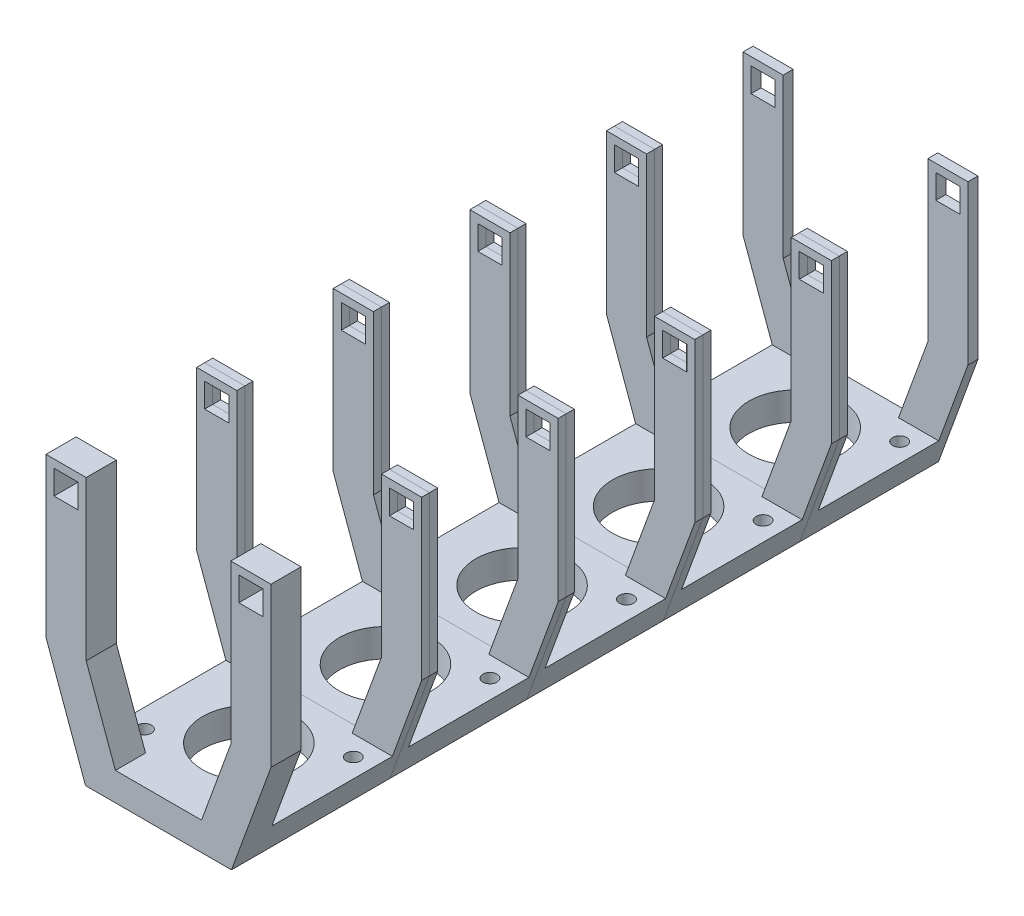
SolidWorks part; units mm, degrees
ref_plane "Front Plane" through (0, 0, 0) normal (0, 0, 1) x (1, 0, 0)
ref_plane "Top Plane" through (0, 0, 0) normal (0, 1, 0) x (1, 0, 0)
ref_plane "Right Plane" through (0, 0, 0) normal (1, 0, 0) x (0, 0, -1)
sketch "Sketch3" plane through (0, 0, 0) normal (0, 0, 1) x (1, 0, 0)
  line L0 (0, 0) -> (46, 0) construction
  line L1 (-3, -3) -> (3, -3) construction
  line L2 (-3, -3) -> (-3, 3) construction
  line L3 (-3, 3) -> (3, 3) construction
  line L4 (3, -3) -> (3, 3) construction
  line L5 (-3, -3) -> (3, 3) construction
  line L6 (-3, 3) -> (3, -3) construction
  line L7 (43, -3) -> (49, -3) construction
  line L8 (43, -3) -> (43, 3) construction
  line L9 (43, 3) -> (49, 3) construction
  line L10 (49, -3) -> (49, 3) construction
  line L11 (43, -3) -> (49, 3) construction
  line L12 (43, 3) -> (49, -3) construction
  line L14 (5, -5) -> (5, 5)
  line L16 (-5, -5) -> (-5, 5)
  line L18 (51, -5) -> (51, 5)
  line L20 (41, -5) -> (41, 5)
  line L21 (-5, -5) -> (-5, -25) construction
  line L22 (-5, -25) -> (51, -25) construction
  line L23 (51, -25) -> (51, -5) construction
  line L24 (23, 0) -> (23, 5) construction
  line L25 (23, 5) -> (8, 5) construction
  line L26 (23, 5) -> (38, 5) construction
  line L27 (8, 5) -> (8, -25) construction
  line L28 (38, 5) -> (38, -25) construction
  line L29 (-5, -5) -> (4.8272, -32)
  line L30 (4.8272, -32) -> (41.1728, -32)
  line L31 (41.1728, -32) -> (51, -5)
  line L32 (5, -5) -> (12.2794, -25)
  line L33 (12.2794, -25) -> (33.7206, -25)
  line L34 (33.7206, -25) -> (41, -5)
  line L35 (2.2794, -25) -> (12.2794, -25)
  line L36 (-5, -5) -> (5, -5) construction
  line L37 (41, -5) -> (51, -5) construction
  line L38 (33.7206, -25) -> (43.7206, -25)
  line L39 (-5, 5) -> (5, 5) construction
  line L40 (41, 5) -> (51, 5) construction
  line L41 (-5, 5) -> (-5, 34.5)
  line L42 (-5, 34.5) -> (5, 34.5)
  line L43 (5, 34.5) -> (5, 5)
  line L44 (41, 5) -> (41, 34.5)
  line L45 (41, 34.5) -> (51, 34.5)
  line L46 (51, 34.5) -> (51, 5)
  line L48 (-3, 26.5) -> (3, 26.5)
  line L49 (-3, 26.5) -> (-3, 32.5)
  line L50 (-3, 32.5) -> (3, 32.5)
  line L51 (3, 26.5) -> (3, 32.5)
  line L52 (-3, 26.5) -> (3, 32.5) construction
  line L53 (-3, 32.5) -> (3, 26.5) construction
  line L54 (43, 26.5) -> (49, 26.5)
  line L55 (43, 26.5) -> (43, 32.5)
  line L56 (43, 32.5) -> (49, 32.5)
  line L57 (49, 26.5) -> (49, 32.5)
  line L58 (43, 26.5) -> (49, 32.5) construction
  line L59 (43, 32.5) -> (49, 26.5) construction
  point P0 (0, 0)
  point P6 (46, 0)
  point P27 (2.2794, -25)
  point P34 (43.7206, -25)
  point P35 (0, 29.5)
  point P46 (46, 29.5)
  point P51 (0, 0)
  point P52 (0, 0)
  dimension "D1" = 40
  dimension "D2" = 6
  dimension "D4" = 30
  dimension "D5" = 30
  dimension "D6" = 7
  dimension "D7" = 20
  dimension "D8" = 20
  dimension "D9" = 20
  dimension "D10" = 20
  dimension "D11" = 29.5
  dimension "D12" = 29.5
  dimension "D13" = 2
  dimension "D14" = 2
  dimension "D3" = 2
extrude "Boss-Extrude1" add sketch "Sketch3" along normal blind 2 contours L29 L35 L32 L14 L16 L4 L1 L2 L3 | L34 L38 L31 L18 L20 L10 L7 L8 L9 | L38 L33 L35 L29 L30 L31 region at (1.3022, 3.1561, 0) region at (23, -28.4236, 0) region at (44.6978, 3.1561, 0)
extrude "Boss-Extrude2" add sketch "Sketch3<4>" against normal blind 30 contours L38 L33 L35 L29 L30 L31 region at (23, -28.4236, 0)
sketch "Sketch3<4>" plane through (0, 0, 0) normal (0, 0, 1) x (1, 0, 0) same geometry as "Sketch3"
sketch "Sketch4" plane through (0, 0, -30) normal (0, 0, -1) x (-1, 0, 0)
  line L0 (5, -5) -> (5, 34.5) construction
  line L2 (-5, -5) -> (-5, 34.5) construction
  line L3 (-5, -5) -> (-12.2794, -25) construction
  line L4 (5, -5) -> (-2.2794, -25) construction
  line L5 (-2.2794, -25) -> (-4.8272, -32) construction
  line L6 (-41.1728, -32) -> (-43.7206, -25) construction
  line L7 (-4.8272, -32) -> (-41.1728, -32) construction
  line L8 (-2.2794, -25) -> (-43.7206, -25) construction
  line L9 (-33.7206, -25) -> (-41, -5) construction
  line L10 (-41, -5) -> (-41, 34.5) construction
  line L11 (-43.7206, -25) -> (-51, -5) construction
  line L12 (-51, -5) -> (-51, 34.5) construction
  line L13 (3, 26.5) -> (-3, 26.5) construction
  line L14 (5, -5) -> (5, 34.5)
  line L16 (-5, -5) -> (-5, 34.5)
  line L17 (-5, -5) -> (-12.2794, -25)
  line L18 (5, -5) -> (-2.2794, -25)
  line L19 (-2.2794, -25) -> (-4.8272, -32)
  line L20 (-41.1728, -32) -> (-43.7206, -25)
  line L21 (-4.8272, -32) -> (-41.1728, -32)
  line L22 (-12.2794, -25) -> (-33.7206, -25)
  line L23 (-33.7206, -25) -> (-41, -5)
  line L24 (-41, -5) -> (-41, 34.5)
  line L25 (-43.7206, -25) -> (-51, -5)
  line L26 (-51, -5) -> (-51, 34.5)
  line L44 (-51, 34.5) -> (-41, 34.5)
  line L45 (-5, 34.5) -> (5, 34.5)
  line L46 (3, 26.5) -> (3, 32.5) construction
  line L47 (3, 32.5) -> (-3, 32.5) construction
  line L48 (-3, 26.5) -> (-3, 32.5) construction
  line L49 (-49, 26.5) -> (-49, 32.5) construction
  line L50 (-43, 26.5) -> (-49, 26.5) construction
  line L51 (-43, 26.5) -> (-43, 32.5) construction
  line L52 (-43, 32.5) -> (-49, 32.5) construction
  line L53 (3, 26.5) -> (-3, 26.5)
  line L54 (3, 26.5) -> (3, 32.5)
  line L55 (3, 32.5) -> (-3, 32.5)
  line L56 (-3, 26.5) -> (-3, 32.5)
  line L57 (-49, 26.5) -> (-49, 32.5)
  line L58 (-43, 26.5) -> (-49, 26.5)
  line L59 (-43, 26.5) -> (-43, 32.5)
  line L60 (-43, 32.5) -> (-49, 32.5)
extrude "Boss-Extrude6" add sketch "Sketch4" along normal blind 2
pattern_linear "LPattern7" count 5 spacing 34 along (0, 0, 1) of bodies 128
sketch "Sketch12" plane through (0, 0, -32) normal (0, 0, -1) x (-1, 0, 0)
  line L0 (-5, 34.5) -> (-5, -5) construction
  line L1 (5, 34.5) -> (-5, 34.5) construction
  line L2 (5, -5) -> (5, 34.5) construction
  line L7 (-5, -5) -> (-12.2794, -25) construction
  line L8 (-4.8272, -32) -> (5, -5) construction
  line L9 (-12.2794, -25) -> (-33.7206, -25) construction
  line L10 (-41.1728, -32) -> (-4.8272, -32) construction
  line L11 (-41, -5) -> (-41, 34.5) construction
  line L12 (-33.7206, -25) -> (-41, -5) construction
  line L13 (-51, -5) -> (-41.1728, -32) construction
  line L18 (-51, 34.5) -> (-51, -5) construction
  line L19 (-41, 34.5) -> (-51, 34.5) construction
  line L20 (-5, 34.5) -> (-5, -5)
  line L21 (5, 34.5) -> (-5, 34.5)
  line L22 (5, -5) -> (5, 34.5)
  line L27 (-5, -5) -> (-12.2794, -25)
  line L28 (-4.8272, -32) -> (5, -5)
  line L29 (-12.2794, -25) -> (-33.7206, -25)
  line L30 (-41.1728, -32) -> (-4.8272, -32)
  line L31 (-41, -5) -> (-41, 34.5)
  line L32 (-33.7206, -25) -> (-41, -5)
  line L33 (-51, -5) -> (-41.1728, -32)
  line L38 (-51, 34.5) -> (-51, -5)
  line L39 (-41, 34.5) -> (-51, 34.5)
  line L40 (-3, 26.5) -> (3, 26.5) construction
  line L41 (3, 26.5) -> (3, 32.5) construction
  line L42 (3, 32.5) -> (-3, 32.5) construction
  line L43 (-3, 32.5) -> (-3, 26.5) construction
  line L44 (-49, 32.5) -> (-49, 26.5) construction
  line L45 (-49, 26.5) -> (-43, 26.5) construction
  line L46 (-43, 26.5) -> (-43, 32.5) construction
  line L47 (-43, 32.5) -> (-49, 32.5) construction
  line L48 (-3, 26.5) -> (3, 26.5)
  line L49 (3, 26.5) -> (3, 32.5)
  line L50 (3, 32.5) -> (-3, 32.5)
  line L51 (-3, 32.5) -> (-3, 26.5)
  line L52 (-49, 32.5) -> (-49, 26.5)
  line L53 (-49, 26.5) -> (-43, 26.5)
  line L54 (-43, 26.5) -> (-43, 32.5)
  line L55 (-43, 32.5) -> (-49, 32.5)
extrude "Boss-Extrude7" add sketch "Sketch12" along normal blind 0.5
sketch "Sketch13" plane through (0, 0, 138) normal (0, 0, 1) x (1, 0, 0)
  line L1 (41, -5) -> (41, 34.5) construction
  line L4 (51, -5) -> (51, 34.5) construction
  line L7 (41.1728, -32) -> (51, -5) construction
  line L8 (33.7206, -25) -> (41, -5) construction
  line L9 (4.8272, -32) -> (41.1728, -32) construction
  line L10 (12.2794, -25) -> (33.7206, -25) construction
  line L11 (5, -5) -> (12.2794, -25) construction
  line L12 (-5, -5) -> (4.8272, -32) construction
  line L13 (5, -5) -> (5, 34.5) construction
  line L18 (-5, -5) -> (-5, 34.5) construction
  line L21 (41, -5) -> (41, 34.5)
  line L24 (51, -5) -> (51, 34.5)
  line L27 (41.1728, -32) -> (51, -5)
  line L28 (33.7206, -25) -> (41, -5)
  line L29 (4.8272, -32) -> (41.1728, -32)
  line L30 (12.2794, -25) -> (33.7206, -25)
  line L31 (5, -5) -> (12.2794, -25)
  line L32 (-5, -5) -> (4.8272, -32)
  line L33 (5, -5) -> (5, 34.5)
  line L38 (-5, -5) -> (-5, 34.5)
  line L40 (-5, 34.5) -> (5, 34.5)
  line L41 (41, 34.5) -> (51, 34.5)
  line L42 (43, 26.5) -> (43, 32.5) construction
  line L43 (43, 26.5) -> (49, 26.5) construction
  line L44 (49, 26.5) -> (49, 32.5) construction
  line L45 (43, 32.5) -> (49, 32.5) construction
  line L46 (-3, 26.5) -> (-3, 32.5) construction
  line L47 (-3, 26.5) -> (3, 26.5) construction
  line L48 (3, 26.5) -> (3, 32.5) construction
  line L49 (-3, 32.5) -> (3, 32.5) construction
  line L50 (43, 26.5) -> (43, 32.5)
  line L51 (43, 26.5) -> (49, 26.5)
  line L52 (49, 26.5) -> (49, 32.5)
  line L53 (43, 32.5) -> (49, 32.5)
  line L54 (-3, 26.5) -> (-3, 32.5)
  line L55 (-3, 26.5) -> (3, 26.5)
  line L56 (3, 26.5) -> (3, 32.5)
  line L57 (-3, 32.5) -> (3, 32.5)
extrude "Boss-Extrude8" add sketch "Sketch13" along normal blind 2
sketch "Sketch15" plane through (0, -25, 0) normal (0, 1, 0) x (1, 0, 0)
  line L0 (23, -104) -> (23, -140) construction
  line L1 (12.2794, -104) -> (33.7206, -104) construction
  line L2 (33.7206, -140) -> (12.2794, -140) construction
  line L3 (2.2794, -121) -> (43.7206, -121) construction
  line L4 (2.2794, -106) -> (2.2794, -136) construction
  line L5 (43.7206, -106) -> (43.7206, -136) construction
  circle A0 centre (23, -121) radius 11.5
  circle A1 centre (23, -121) radius 15 construction
  circle A2 centre (7, -131) radius 1.75
  circle A3 centre (39, -111) radius 1.75
  dimension "D1" = 23
  dimension "D2" = 30
  dimension "D3" = 3.5
  dimension "D4" = 16
  dimension "D5" = 16
  dimension "D6" = 10
  dimension "D7" = 10
extrude "Cut-Extrude5" cut sketch "Sketch15" against normal up to surface (7 mm away) up to face at (23, -32, 122)
pattern_linear "LPattern8" count 5 spacing 34 along (0, 0, -1) of "Cut-Extrude5"
sketch "Sketch16" plane through (0, 0, 140) normal (0, 0, 1) x (1, 0, 0)
  line L0 (41.1728, -32) -> (51, -5) construction
  line L5 (51, -5) -> (51, 34.5) construction
  line L6 (51, 34.5) -> (41, 34.5) construction
  line L7 (41, 34.5) -> (41, -5) construction
  line L8 (41, -5) -> (33.7206, -25) construction
  line L9 (33.7206, -25) -> (12.2794, -25) construction
  line L10 (4.8272, -32) -> (41.1728, -32) construction
  line L11 (12.2794, -25) -> (5, -5) construction
  line L12 (-5, -5) -> (4.8272, -32) construction
  line L13 (-5, 34.5) -> (-5, -5) construction
  line L18 (5, -5) -> (5, 34.5) construction
  line L19 (5, 34.5) -> (-5, 34.5) construction
  line L20 (41.1728, -32) -> (51, -5)
  line L25 (51, -5) -> (51, 34.5)
  line L26 (51, 34.5) -> (41, 34.5)
  line L27 (41, 34.5) -> (41, -5)
  line L28 (41, -5) -> (33.7206, -25)
  line L29 (33.7206, -25) -> (12.2794, -25)
  line L30 (4.8272, -32) -> (41.1728, -32)
  line L31 (12.2794, -25) -> (5, -5)
  line L32 (-5, -5) -> (4.8272, -32)
  line L33 (-5, 34.5) -> (-5, -5)
  line L38 (5, -5) -> (5, 34.5)
  line L39 (5, 34.5) -> (-5, 34.5)
  line L40 (43, 26.5) -> (49, 26.5) construction
  line L41 (49, 26.5) -> (49, 32.5) construction
  line L42 (49, 32.5) -> (43, 32.5) construction
  line L43 (43, 32.5) -> (43, 26.5) construction
  line L44 (-3, 32.5) -> (-3, 26.5) construction
  line L45 (-3, 26.5) -> (3, 26.5) construction
  line L46 (3, 26.5) -> (3, 32.5) construction
  line L47 (3, 32.5) -> (-3, 32.5) construction
  line L48 (43, 26.5) -> (49, 26.5)
  line L49 (49, 26.5) -> (49, 32.5)
  line L50 (49, 32.5) -> (43, 32.5)
  line L51 (43, 32.5) -> (43, 26.5)
  line L52 (-3, 32.5) -> (-3, 26.5)
  line L53 (-3, 26.5) -> (3, 26.5)
  line L54 (3, 26.5) -> (3, 32.5)
  line L55 (3, 32.5) -> (-3, 32.5)
extrude "Boss-Extrude9" add sketch "Sketch16" along normal blind 3.5
